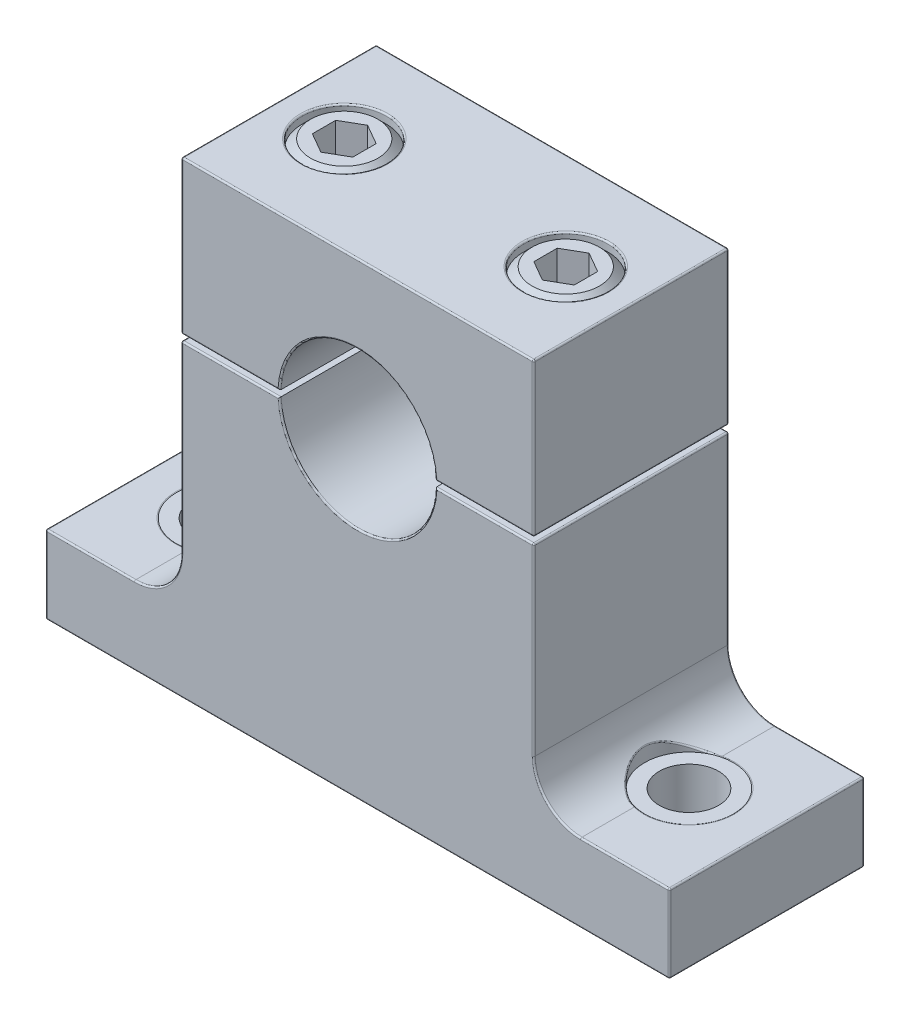
SolidWorks part; units mm, degrees
ref_plane "Front Plane" through (0, 0, 0) normal (0, 0, 1) x (1, 0, 0)
ref_plane "Top Plane" through (0, 0, 0) normal (0, 1, 0) x (1, 0, 0)
ref_plane "Right Plane" through (0, 0, 0) normal (1, 0, 0) x (0, 0, -1)
sketch "Sketch1" plane through (0, 0, 0) normal (0, 0, 1) x (1, 0, 0)
  line L0 (0, 12.7) -> (0, -25.4) construction
  line L1 (25.4, -25.4) -> (-25.4, -25.4) construction
  line L2 (-14.351, 12.7) -> (14.351, 12.7) construction
  line L3 (0, 0.25) -> (0, -0.25) construction
  line L4 (-9.017, 0) -> (9.017, 0) construction
  line L5 (-19.05, -19.05) -> (19.05, -19.05) construction
  line L6 (-9.017, 12.7) -> (-9.017, -25.4) construction
  line L7 (-12.446, 12.7) -> (-5.588, 12.7) construction
  line L8 (-11.0998, -25.4) -> (-6.9342, -25.4) construction
  line L9 (-21.463, -19.05) -> (-16.637, -19.05) construction
  line L10 (-22.6695, -19.05) -> (-15.4305, -19.05) construction
  circle A0 centre (0, 0) radius 6.35 construction
  point P7 (0, 0)
  point P8 (0, -25.4)
  point P11 (0, -19.05)
  point P14 (0, 12.7)
  point P15 (0, 0)
  point P20 (0, -19.05)
  point P23 (-9.017, 8.5344)
  point P26 (-9.017, 12.7)
  point P27 (-9.017, -25.4)
  point P30 (-19.05, -19.05)
  point P35 (-19.05, -19.05)
  dimension "D3" = 4.1656
  dimension "D4" = 7.239
sketch "Sketch2" plane through (0, 0, 0) normal (0, 0, 1) x (1, 0, 0)
  line L0 (-14.351, 12.7) -> (14.351, 12.7)
  line L1 (25.4, -25.4) -> (-25.4, -25.4) construction
  line L2 (25.4, -25.4) -> (-25.4, -25.4)
  line L3 (-25.4, -25.4) -> (-25.4, -19.05)
  line L4 (-25.4, -19.05) -> (-18.161, -19.05)
  line L5 (-14.351, -15.24) -> (-14.351, -0.25)
  line L6 (14.351, 12.7) -> (14.351, 0.25)
  line L7 (18.161, -19.05) -> (25.4, -19.05)
  line L8 (25.4, -19.05) -> (25.4, -25.4)
  line L9 (-14.351, 0.25) -> (-6.3451, 0.25)
  line L10 (-14.351, -0.25) -> (-6.3451, -0.25)
  line L11 (-14.351, 0.25) -> (-14.351, 12.7)
  line L12 (14.351, -0.25) -> (14.351, -15.24)
  line L13 (6.3451, 0.25) -> (14.351, 0.25)
  line L14 (6.3451, -0.25) -> (14.351, -0.25)
  circle A0 centre (0, 0) radius 6.35 construction
  arc A1 (-6.3451, -0.25) -> (6.3451, -0.25) centre (0, 0) ccw
  arc A2 (6.3451, 0.25) -> (-6.3451, 0.25) centre (0, 0) ccw
  arc A3 (14.351, -15.24) -> (18.161, -19.05) centre (18.161, -15.24) ccw
  arc A4 (-18.161, -19.05) -> (-14.351, -15.24) centre (-18.161, -15.24) ccw
  dimension "D1" = 3.81
extrude "Boss-Extrude1" add sketch "Sketch2" along normal mid plane 15.875
sketch "Sketch3" plane through (0, -19.05, 0) normal (0, 1, 0) x (1, 0, 0)
  line L0 (25.4, 0) -> (-25.4, 0) construction
  line L1 (-9.017, 0) -> (9.017, 0) construction
  circle A0 centre (-9.017, 0) radius 3.429
  circle A1 centre (9.017, 0) radius 3.429
  circle A2 centre (-19.05, 0) radius 2.413
  circle A3 centre (19.05, 0) radius 2.413
  circle A4 centre (-19.05, 0) radius 3.6195 construction
  circle A5 centre (19.05, 0) radius 3.6195 construction
  circle A6 centre (-9.017, 0) radius 3.429 construction
  circle A9 centre (9.017, 0) radius 3.429 construction
  point P6 (0, 0)
  point P16 (0, 0)
sketch "Sketch4" plane through (0, -19.05, 0) normal (0, 1, 0) x (1, 0, 0)
  circle A0 centre (-19.05, 0) radius 2.413 construction
  circle A1 centre (19.05, 0) radius 2.413 construction
  circle A2 centre (-19.05, 0) radius 2.413
  circle A3 centre (19.05, 0) radius 2.413
  point P0 (-19.05, 0)
extrude "Cut-Extrude1" cut sketch "Sketch4" against normal through all
sketch "Sketch5" plane through (0, -19.05, 0) normal (0, 1, 0) x (1, 0, 0)
  circle A0 centre (19.05, 0) radius 3.6195 construction
  circle A1 centre (-19.05, 0) radius 3.6195 construction
  circle A2 centre (19.05, 0) radius 3.6195
  circle A3 centre (-19.05, 0) radius 3.6195
extrude "Cut-Extrude2" cut sketch "Sketch5" against normal blind 0.02 and the other way through all
sketch "Sketch6" plane through (0, 12.7, 0) normal (0, 1, 0) x (1, 0, 0)
  circle A0 centre (9.017, 0) radius 3.429 construction
  circle A1 centre (-9.017, 0) radius 3.429 construction
  circle A2 centre (9.017, 0) radius 3.429
  circle A3 centre (-9.017, 0) radius 3.429
extrude "Cut-Extrude3" cut sketch "Sketch6" against normal up to vertex (4.1656 mm away) up to point (-9.017, 8.5344, 0)
sketch "Sketch8" plane through (0, 8.5344, 0) normal (0, 1, 0) x (1, 0, 0)
  circle A2 centre (9.017, 0) radius 2.0828
  circle A3 centre (-9.017, 0) radius 2.0828
extrude "Cut-Extrude4" cut sketch "Sketch8" against normal through all
sketch "Sketch10" plane through (0, 0, 0) normal (0, 0, 1) x (1, 0, 0)
  line L4 (-9.017, 12.7) -> (-5.588, 12.7)
  line L5 (-5.588, 12.7) -> (-5.588, 8.5344)
  line L6 (-5.588, 8.5344) -> (-6.9342, 8.5344)
  line L7 (-6.9342, 8.5344) -> (-6.9342, -25.4)
  line L10 (-6.9342, -25.4) -> (-9.017, -25.4)
  line L11 (-9.017, -25.4) -> (-9.017, 12.7)
revolve "Revolve1" add sketch "Sketch10" angle 360 about L11
sketch "Sketch11" plane through (0, 12.7, 0) normal (0, 1, 0) x (1, 0, 0)
  line L1 (-9.017, 1.9005) -> (-10.6629, 0.9503)
  line L2 (-10.6629, 0.9503) -> (-10.6629, -0.9503)
  line L3 (-10.6629, -0.9503) -> (-9.017, -1.9005)
  line L4 (-9.017, -1.9005) -> (-7.3711, -0.9503)
  line L5 (-7.3711, -0.9503) -> (-7.3711, 0.9503)
  line L6 (-7.3711, 0.9503) -> (-9.017, 1.9005)
  circle A0 centre (-9.017, 0) radius 1.6459 construction
  circle A1 centre (-9.017, 0) radius 3.429 construction
  circle A2 centre (-9.017, 0) radius 3.429 construction
  dimension "D1" = 6.858
  dimension "D2" = 3.2918
extrude "Cut-Extrude5" cut sketch "Sketch11" against normal blind 3
chamfer "Chamfer1" distance 0.6858 angle 45 1 edges at (-5.588, 12.7, 0)
mirror "Mirror1" about plane through (0, 0, 0) normal (1, 0, 0) of bodies 112
fillet "Fillet1" radius 0.127 36 edges at (15.4428, -17.9097, 0.2976) (-15.4428, -17.9097, -0.2976) (16.637, -25.4, 0) (-21.463, -25.4, 0) (-11.0998, -25.4, 0) (6.9342, -25.4, 0) (25.4, -25.4, 0) (25.4, -19.05, 0) (14.351, -0.25, 0) (-14.351, -0.25, 0) (-25.4, -19.05, 0) (-25.4, -25.4, 0) (21.7805, -19.05, -7.9375) (15.4669, -17.9341, -7.9375) (14.351, -7.745, -7.9375) (10.348, -0.25, -7.9375) (0, -6.35, -7.9375) (-10.348, -0.25, -7.9375) (-14.351, -7.745, -7.9375) (-15.4669, -17.9341, -7.9375) (-21.7805, -19.05, -7.9375) (-25.4, -22.225, -7.9375) (0, -25.4, -7.9375) (25.4, -22.225, -7.9375) (0, -25.4, 7.9375) (-25.4, -22.225, 7.9375) (-21.7805, -19.05, 7.9375) (-15.4669, -17.9341, 7.9375) (-14.351, -7.745, 7.9375) (-10.348, -0.25, 7.9375) (0, -6.35, 7.9375) (10.348, -0.25, 7.9375) (14.351, -7.745, 7.9375) (15.4669, -17.9341, 7.9375) (21.7805, -19.05, 7.9375) (25.4, -22.225, 7.9375)
fillet "Fillet2" radius 0.127 18 edges at (14.351, 0.25, 0) (-10.348, 0.25, -7.9375) (0, 6.35, -7.9375) (10.348, 0.25, -7.9375) (14.351, 6.475, -7.9375) (-14.351, 0.25, 0) (-14.351, 6.475, -7.9375) (14.351, 12.7, 0) (-14.351, 12.7, 0) (0, 12.7, -7.9375) (-12.446, 12.7, 0) (5.588, 12.7, 0) (0, 12.7, 7.9375) (14.351, 6.475, 7.9375) (10.348, 0.25, 7.9375) (0, 6.35, 7.9375) (-10.348, 0.25, 7.9375) (-14.351, 6.475, 7.9375)
ref_plane "Contact Plane 1" through (0, -25.4, 0) normal (0, -1, 0) x (-1, 0, 0)
ref_axis "Center Axis 1" through (0, 0, 7.8105) along (0, 0, -1)
equation "\"D3@Sketch1\"=\"G@Sketch1\""
equation "\"D4@Sketch1\"=\"K@Sketch1\"*1.5"
equation "\"D2@Sketch11\"=\"D1@Sketch11\"*.48"
equation "\"D1@Sketch2\"=\"Height@Sketch1\"*.1"
equation "\"D1@Chamfer1\"=\"Screw Head Dia@Sketch1\"*.1"
